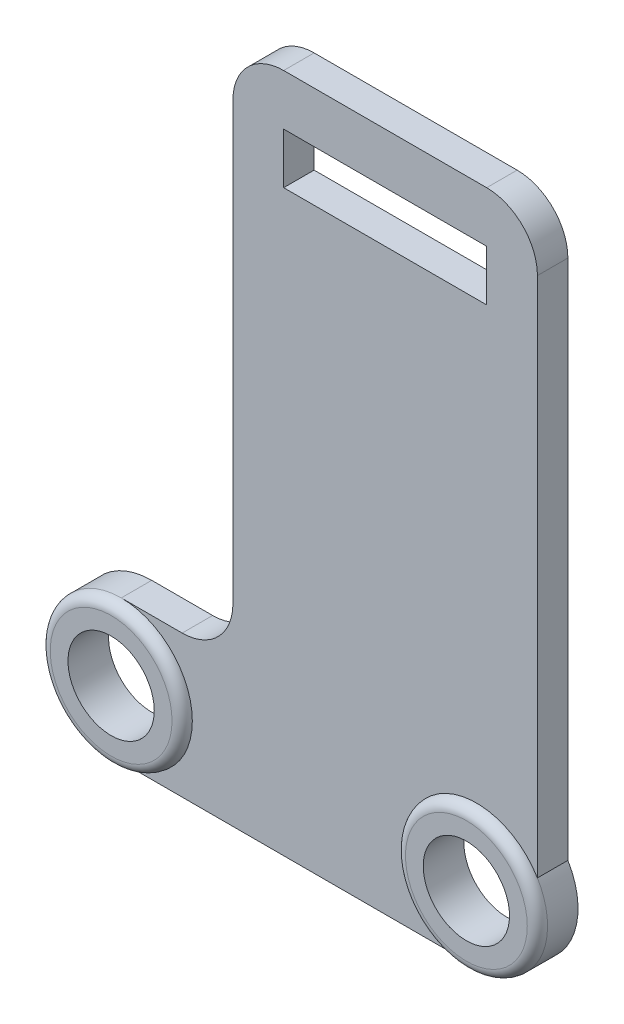
SolidWorks part; units mm, degrees
material "ABS"
ref_plane "Front Plane" through (0, 0, 0) normal (0, 0, 1) x (1, 0, 0)
ref_plane "Top Plane" through (0, 0, 0) normal (0, 1, 0) x (1, 0, 0)
ref_plane "Right Plane" through (0, 0, 0) normal (1, 0, 0) x (0, 0, -1)
sketch "Sketch1" plane through (0, 0, 0) normal (0, 0, 1) x (1, 0, 0)
  line L0 (0, 26) -> (0, 33.5) construction
  line L1 (9, -33.5) -> (-26, -33.5)
  line L3 (10, 33.5) -> (-10, 33.5)
  line L4 (-15, -14.5) -> (-15, 28.5)
  line L5 (14.0406, -31.3572) -> (-15, 33.5) construction
  line L6 (15, 33.5) -> (-15, -33.5) construction
  line L7 (-10, 28.5) -> (10, 28.5)
  line L8 (-10, 28.5) -> (-10, 23.5)
  line L9 (-10, 23.5) -> (10, 23.5)
  line L10 (10, 28.5) -> (10, 23.5)
  line L11 (-10, 28.5) -> (10, 23.5) construction
  line L12 (-10, 23.5) -> (10, 28.5) construction
  line L13 (9, -26.5) -> (-26, -26.5) construction
  line L14 (-26, -19.5) -> (-20, -19.5)
  line L15 (15, -22.8944) -> (15, 28.5)
  line L16 (-15, -19.5) -> (-15, -33.5) construction
  line L17 (15, -22.8944) -> (15, -33.5) construction
  line L18 (14.0406, -31.3572) -> (15, -33.5) construction
  circle A0 centre (9, -26.5) radius 4.25
  circle A1 centre (-26, -26.5) radius 4.25
  arc A2 (-26, -19.5) -> (-26, -33.5) centre (-26, -26.5) ccw
  arc A3 (9, -33.5) -> (15, -22.8944) centre (9, -26.5) ccw
  arc A4 (-20, -19.5) -> (-15, -14.5) centre (-20, -14.5) ccw
  arc A5 (15, 28.5) -> (10, 33.5) centre (10, 28.5) ccw
  arc A6 (-10, 33.5) -> (-15, 28.5) centre (-10, 28.5) ccw
  point P0 (0, 0)
  point P5 (0, 26)
  dimension "D6" = 8.5
  dimension "D7" = 35
  dimension "D8" = 7
  dimension "D9" = 6
  dimension "D10" = 8.5
  dimension "D11" = 14
  dimension "D12" = 5
  dimension "D1" = 30
  dimension "D2" = 33.5
  dimension "D3" = 20
  dimension "D4" = 5
  dimension "D5" = 5
extrude "Boss-Extrude1" add sketch "Sketch1" along normal blind 3
sketch "Sketch2" plane through (0, 0, 3) normal (0, 0, 1) x (1, 0, 0)
  circle A0 centre (-26, -26.5) radius 7
  circle A1 centre (9, -26.5) radius 7
  circle A2 centre (-26, -26.5) radius 4.25
  circle A3 centre (9, -26.5) radius 4.25
  circle A4 centre (-26, -26.5) radius 4.25 construction
  circle A5 centre (9, -26.5) radius 4.25 construction
  arc A6 (-26, -19.5) -> (-26, -33.5) centre (-26, -26.5) ccw construction
  arc A7 (9, -33.5) -> (15, -22.8944) centre (9, -26.5) ccw construction
extrude "Boss-Extrude2" add sketch "Sketch2" along normal blind 1
fillet "Fillet1" radius 1 2 edges at (16, -26.5, 4) (-19, -26.5, 4)
